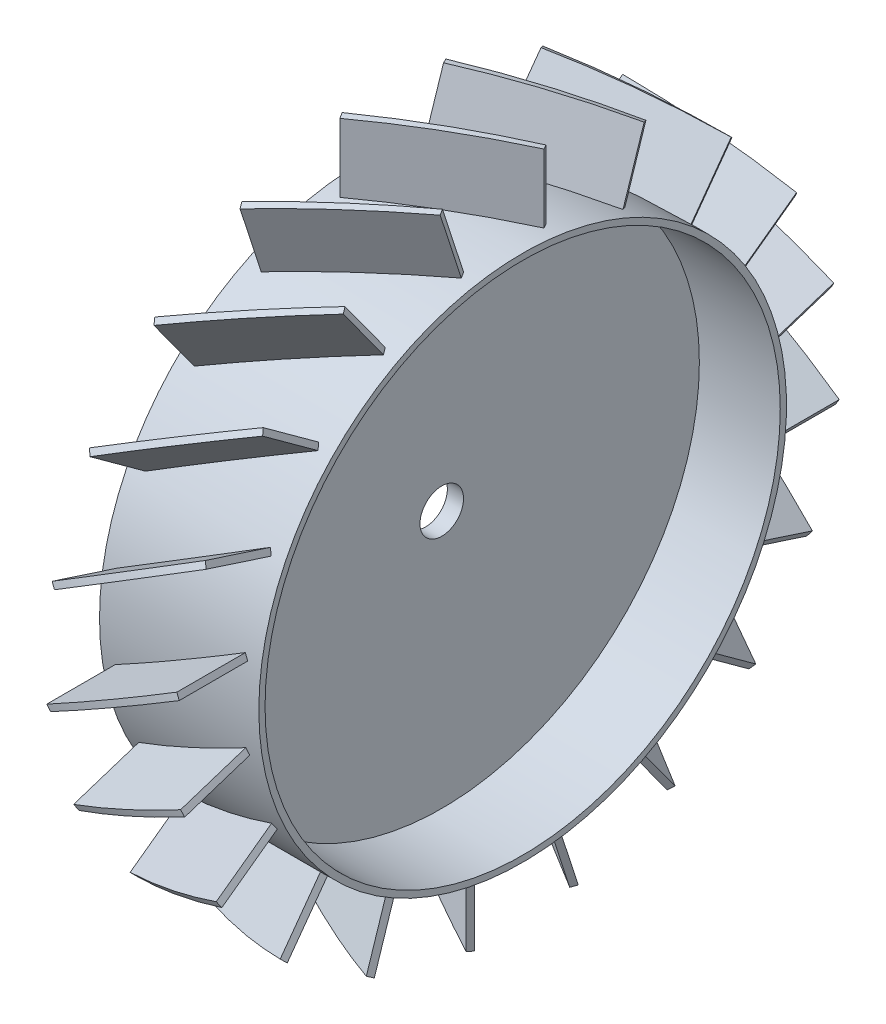
SolidWorks part; units mm, degrees
ref_plane "Front Plane" through (0, 0, 0) normal (0, 0, 1) x (1, 0, 0)
ref_plane "Top Plane" through (0, 0, 0) normal (0, 1, 0) x (1, 0, 0)
ref_plane "Right Plane" through (0, 0, 0) normal (1, 0, 0) x (0, 0, -1)
sketch "Sketch1" plane through (0, 0, 0) normal (0, 1, 0) x (1, 0, 0)
  line L0 (3.302, 0) -> (3.302, 52.578)
  line L1 (3.302, 52.578) -> (19.812, 52.578)
  line L2 (19.812, 52.578) -> (19.812, 53.848)
  line L3 (19.812, 53.848) -> (-12.7, 53.848)
  line L4 (-12.7, 53.848) -> (-12.7, 52.578)
  line L5 (-12.7, 52.578) -> (0, 52.578)
  line L6 (0, 52.578) -> (0, 0)
  line L7 (0, 0) -> (3.302, 0)
  dimension "D1" = 3.302
  dimension "D2" = 1.27
  dimension "D3" = 52.578
  dimension "D4" = 32.512
  dimension "D5" = 12.7
revolve "Revolve1" add sketch "Sketch1" angle 360 about L7
ref_plane "Plane1" through (0, 0, 83.82) normal (0, 0, 1) x (1, 0, 0)
sketch "Sketch2" plane through (0, 0, 83.82) normal (0, 0, 1) x (1, 0, 0)
  line L0 (-9.3247, -8.1699) -> (17.0717, 7.0701)
  line L1 (17.0717, 7.0701) -> (16.4367, 8.1699)
  line L3 (16.4367, 8.1699) -> (-9.9597, -7.0701)
  line L4 (-9.9597, -7.0701) -> (-9.3247, -8.1699)
  line L5 (-12.7, 0) -> (19.812, 0) construction
  line L6 (-12.7, 53.848) -> (-12.7, -53.848) construction
  line L7 (19.812, -53.848) -> (19.812, 53.848) construction
  line L8 (3.8735, -0.5499) -> (3.2385, 0.5499) construction
  point P4 (3.556, 0)
  point P13 (3.556, 0)
  dimension "D1" = 1.27
  dimension "D2" = 30
  dimension "D3" = 30.48
extrude "Boss-Extrude1" add sketch "Sketch2" along normal blind 13.97 from surface starting at face at (-12.7, 0, 53.848)
pattern_circular "CirPattern15" count 20 over 360 about axis through (19.812, 0, 0) along (-1, 0, 0) of "Boss-Extrude1"
sketch "Sketch7" plane through (0, 0, 0) normal (-1, 0, 0) x (0, 0, 1)
  circle A0 centre (0, 0) radius 4.445
  dimension "D1" = 8.89
extrude "Cut-Extrude1" cut sketch "Sketch7" against normal through all
